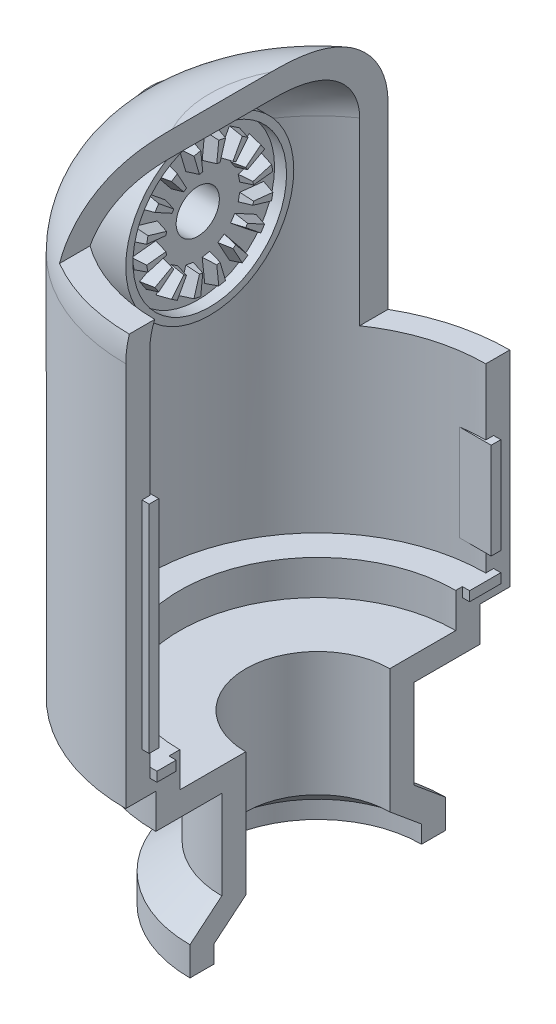
SolidWorks part; units mm, degrees
ref_plane "정면" through (0, 0, 0) normal (0, 0, 1) x (1, 0, 0)
ref_plane "윗면" through (0, 0, 0) normal (0, 1, 0) x (1, 0, 0)
ref_plane "우측면" through (0, 0, 0) normal (1, 0, 0) x (0, 0, -1)
sketch "스케치1" plane through (0, 0, 0) normal (0, 1, 0) x (1, 0, 0)
  circle A0 centre (0, 0) radius 16
  dimension "D1" = 32
extrude "보스-돌출1" add sketch "스케치1" along normal blind 54
sketch "스케치2" plane through (0, 0, 0) normal (0, 0, 1) x (1, 0, 0)
  line L0 (0, 0) -> (0, 55.3244) construction
  line L1 (19.2448, 14.9) -> (13.5, 14.9)
  line L2 (13.5, 14.9) -> (13.5, 12)
  line L3 (13.5, 12) -> (8, 12)
  line L4 (8, 12) -> (8, 4.6)
  line L5 (8, 4.6) -> (10.65, 2.4)
  line L6 (10.65, 2.4) -> (10.65, 0)
  line L7 (-16, 0) -> (16, 0) construction
  line L8 (10.65, 0) -> (19.2448, 0)
  line L9 (19.2448, 0) -> (19.2448, 14.9)
  line L10 (16, 0) -> (16, 54) construction
  dimension "D1" = 14.9
  dimension "D2" = 12
  dimension "D3" = 13.5
  dimension "D4" = 8
  dimension "D5" = 7.4
  dimension "D6" = 2.4
  dimension "D7" = 10.65
revolve "컷-회전1" cut sketch "스케치2" angle 360 about L0
fillet "필렛1" radius 7 1 edges at (0, 54, 16)
shell "쉘1" thickness 2
sketch "스케치3" plane through (0, 0, 0) normal (0, 0, 1) x (1, 0, 0)
  line L0 (0, 0) -> (0, 55.5876)
  line L1 (-10.65, 0) -> (10.65, 0) construction
  line L2 (0, 55.5876) -> (17.9947, 55.5876)
  line L3 (17.9947, 55.5876) -> (17.9947, 0)
  line L4 (17.9947, 0) -> (0, 0)
extrude "컷-돌출1" cut sketch "스케치3" against normal through all both and the other way through all
sketch "스케치4" plane through (0, 54, 0) normal (0, 1, 0) x (1, 0, 0)
  line L0 (-8, 16.4729) -> (-8, -16.9798)
  line L1 (-8, -16.9798) -> (0, -16.9798)
  line L2 (0, -16.9798) -> (0, 16.4729)
  line L3 (0, 16.4729) -> (-8, 16.4729)
  dimension "D1" = 8
extrude "컷-돌출3" cut sketch "스케치4" against normal blind 5
sketch "스케치5" plane through (0, 54, 0) normal (0, 1, 0) x (1, 0, 0)
  line L0 (-8, 16.3949) -> (-8, 0)
  line L1 (-8, 4.1231) -> (-8, -4.1231) construction
  line L2 (-8, 0) -> (0, 0)
  line L3 (0, 0) -> (0, 16.3949)
  line L4 (0, 16.3949) -> (-8, 16.3949)
extrude "컷-돌출4" cut sketch "스케치5" against normal blind 22
ref_plane "평면1" through (-9, 0, 0) normal (1, 0, 0) x (0, 0, -1)
sketch "스케치6" plane through (-9, 0, 0) normal (1, 0, 0) x (0, 0, -1)
  line L0 (0, 0) -> (0, 59.8625) construction
  circle A0 centre (0, 45) radius 7
  dimension "D1" = 14
  dimension "D2" = 45
extrude "보스-돌출2" add sketch "스케치6" against normal up to surface (3.1244 mm away)
sketch "스케치7" plane through (-9, 0, 0) normal (1, 0, 0) x (0, 0, -1)
  circle A0 centre (0, 45) radius 1.8
  dimension "D1" = 3.6
extrude "컷-돌출5" cut sketch "스케치7" against normal through all
sketch "스케치8" plane through (-9, 0, 0) normal (1, 0, 0) x (0, 0, -1)
  circle A0 centre (0, 45) radius 6.4
  dimension "D1" = 12.8
extrude "컷-돌출6" cut sketch "스케치8" against normal blind 1
sketch "스케치9" plane through (-10, 0, 0) normal (1, 0, 0) x (0, 0, -1)
  line L0 (0, 45) -> (0, 52.7764) construction
  line L1 (0, 45) -> (1.6353, 53.2211) construction
  line L2 (0.3707, 48.4948) -> (0.5826, 50.4919)
  line L3 (0.5826, 50.4919) -> (1.5634, 50.2968)
  line L4 (1.5634, 50.2968) -> (0.9949, 48.3707)
  line L5 (0.9949, 48.3707) -> (0.3707, 48.4948)
  point P15 (0.6828, 48.4327)
  dimension "D1" = 1
  dimension "D2" = 2
  dimension "D3" = 3.5
  dimension "D4" = 11.25
extrude "보스-돌출3" add sketch "스케치9" along normal up to surface (1 mm away) draft 11
pattern_circular "원형 패턴1" count 16 over 360 about axis through (0, 45, 0) along (1, 0, 0) of "보스-돌출3"
sketch "스케치10" plane through (0, 0, 0) normal (1, 0, 0) x (0, 0, -1)
  line L0 (-13.85, 18.5) -> (-14.65, 18.5)
  line L2 (-14.65, 18.5) -> (-14.65, 36.5)
  line L3 (-14.65, 36.5) -> (-13.85, 36.5)
  line L4 (-13.85, 36.5) -> (-13.85, 18.5)
  line L5 (-14, 16.9) -> (-14, 16.1)
  line L6 (-14, 16.1) -> (-12.4, 16.1)
  line L7 (-12.4, 16.1) -> (-12.4, 16.9)
  line L9 (-12.4, 16.9) -> (-14, 16.9)
  line L10 (12.05, 16.9) -> (12.05, 16.1)
  line L11 (14, 16.9) -> (11.5, 16.9) construction
  line L12 (12.05, 16.1) -> (14.65, 16.1)
  line L13 (14.65, 16.1) -> (14.65, 16.9)
  line L14 (14.65, 16.9) -> (12.05, 16.9)
  line L15 (13.85, 18.5) -> (14.65, 18.5)
  line L17 (14.65, 18.5) -> (14.65, 26.5)
  line L18 (14.65, 26.5) -> (13.85, 26.5)
  line L19 (13.85, 26.5) -> (13.85, 18.5)
  line L20 (14, 16.9) -> (-14, 16.9) construction
  line L21 (0, 0) -> (0, 44.5321) construction
  point P2 (0, 0)
  point P3 (0, 0)
  point P22 (-12.75, 16.1)
  point P28 (0, 0)
  point P29 (0, 0)
  dimension "D1" = 0.8
  dimension "D2" = 1.6
  dimension "D3" = 18
  dimension "D4" = 8
  dimension "D5" = 27.7
  dimension "D6" = 2.6
  dimension "D7" = 1.6
extrude "보스-돌출4" add sketch "스케치10" along normal blind 0.6 and the other way blind 6
